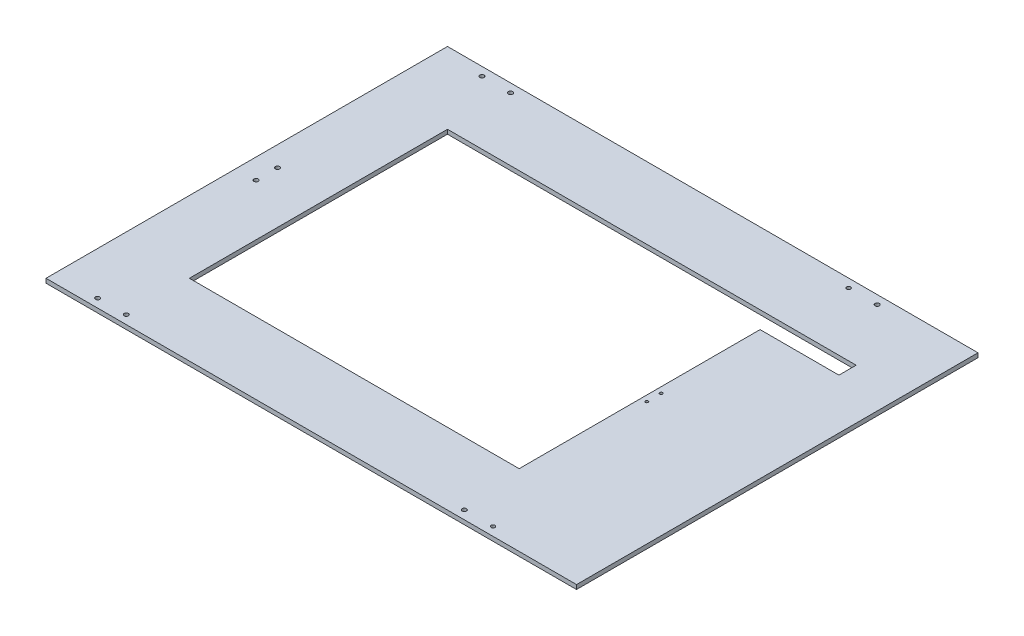
SolidWorks part; units mm, degrees
ref_plane "Front Plane" through (0, 0, 0) normal (0, 0, 1) x (1, 0, 0)
ref_plane "Top Plane" through (0, 0, 0) normal (0, 1, 0) x (1, 0, 0)
ref_plane "Right Plane" through (0, 0, 0) normal (1, 0, 0) x (0, 0, -1)
sketch "Sketch1" plane through (0, 0, 0) normal (0, 1, 0) x (1, 0, 0)
  line L1 (0, 0) -> (370, 0)
  line L2 (0, 0) -> (0, 280)
  line L3 (0, 280) -> (370, 280)
  line L4 (370, 0) -> (370, 280)
  line L5 (50, 50) -> (280, 50)
  line L6 (50, 50) -> (50, 230)
  line L7 (50, 230) -> (280, 230)
  line L8 (280, 50) -> (280, 230)
  line L9 (50, 280) -> (50, 274) construction
  line L10 (50, 274) -> (30, 274) construction
  line L12 (185, 280) -> (185, 0) construction
  line L13 (0, 140) -> (370, 140) construction
  line L14 (284, 140) -> (284, 145) construction
  line L15 (284, 140) -> (284, 135) construction
  circle A0 centre (30, 274) radius 1.5
  circle A1 centre (50, 274) radius 1.5692
  circle A2 centre (30, 6) radius 1.5
  circle A3 centre (50, 6) radius 1.5
  circle A4 centre (285.7569, 273.9854) radius 1.3573
  circle A5 centre (305.7569, 273.9346) radius 1.5
  circle A6 centre (285.7569, 6.0015) radius 1.5
  circle A7 centre (305.7569, 6.0068) radius 1.3225
  circle A8 centre (284, 145) radius 1
  circle A9 centre (284, 135) radius 1
  dimension "D11" = 3
  dimension "D12" = 2
  dimension "D1" = 370
  dimension "D2" = 280
  dimension "D3" = 230
  dimension "D4" = 50
  dimension "D5" = 50
  dimension "D6" = 50
  dimension "D8" = 6
  dimension "D10" = 20
  dimension "D13" = 4
  dimension "D14" = 10
  dimension "D15" = 20
  dimension "D16" = 20
  dimension "D17" = 20
extrude "Boss-Extrude1" add sketch "Sketch1" along normal blind 3
sketch "Sketch2" plane through (0, 3, 0) normal (0, 1, 0) x (1, 0, 0)
  line L1 (280, 230) -> (335, 230)
  line L2 (280, 230) -> (280, 218)
  line L3 (280, 218) -> (335, 218)
  line L4 (335, 230) -> (335, 218)
  dimension "D1" = 55
  dimension "D2" = 12
extrude "Cut-Extrude1" cut sketch "Sketch2" against normal blind 10
sketch "Sketch3" plane through (0, 3, 0) normal (0, 1, 0) x (1, 0, 0)
  line L0 (14, 140) -> (14, 147.5) construction
  line L3 (14, 147.5) -> (14, 140) construction
  line L4 (14, 140) -> (0, 140) construction
  line L5 (0, 280) -> (0, 0) construction
  line L6 (14, 140) -> (14, 132.5) construction
  circle A0 centre (14, 147.5) radius 1.5
  circle A1 centre (14, 132.5) radius 1.5
  dimension "D1" = 3
  dimension "D2" = 3
  dimension "D3" = 14
  dimension "D4" = 15
extrude "Cut-Extrude2" cut sketch "Sketch3" against normal blind 10
